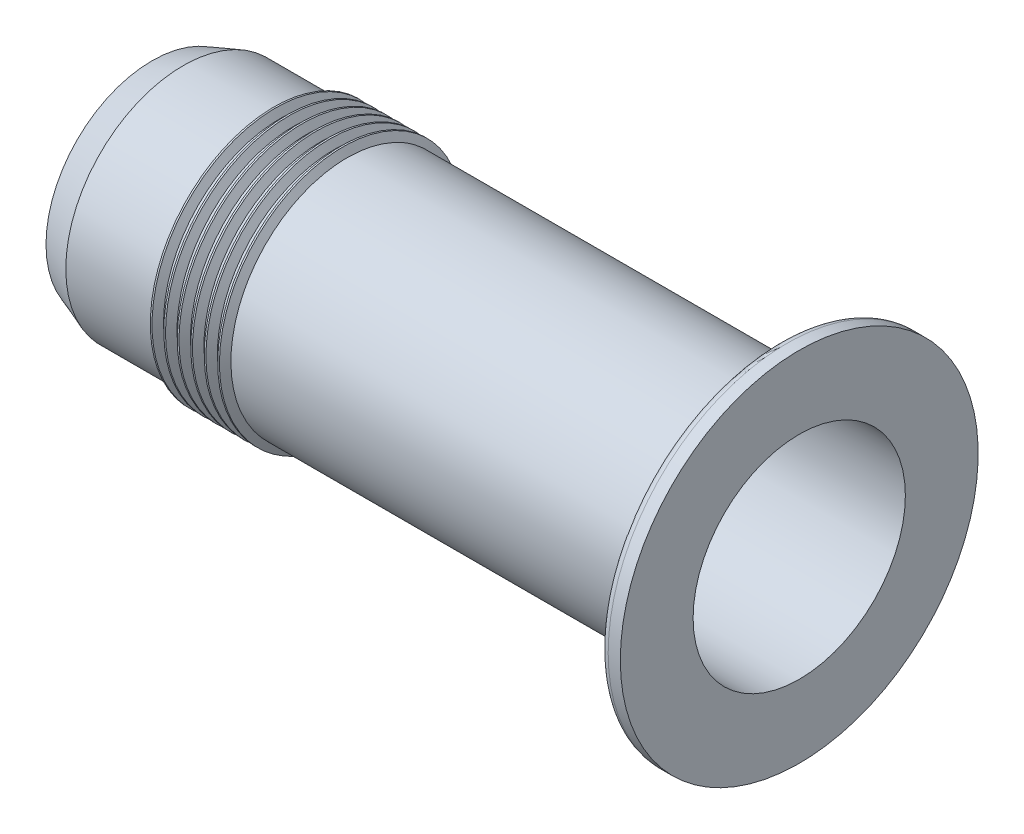
SolidWorks part; units mm, degrees
ref_plane "Front Plane" through (0, 0, 0) normal (0, 0, 1) x (1, 0, 0)
ref_plane "Top Plane" through (0, 0, 0) normal (0, 1, 0) x (1, 0, 0)
ref_plane "Right Plane" through (0, 0, 0) normal (1, 0, 0) x (0, 0, -1)
sketch "Sketch1" plane through (0, 0, 0) normal (0, 0, 1) x (1, 0, 0)
  line L0 (0, 0) -> (109.1124, 0) construction
  line L1 (0, 16.6624) -> (101.6, 16.6624)
  line L4 (19.05, 18.4404) -> (98.425, 18.4404)
  line L5 (101.6, 18.4404) -> (101.6, 16.6624)
  line L6 (0, 16.6624) -> (0, 0) construction
  line L7 (19.05, 18.4404) -> (4.885, 18.4404)
  line L9 (101.6, 18.4404) -> (101.6, 28.0924)
  line L10 (101.6, 28.0924) -> (98.425, 28.0924)
  line L11 (98.425, 28.0924) -> (98.425, 18.4404)
  line L12 (0, 16.6624) -> (4.885, 18.4404)
  dimension "D1" = 16.6624
  dimension "D2" = 1.778
  dimension "D3" = 11.43
  dimension "D4" = 3.175
  dimension "D5" = 101.6
  dimension "D6" = 20
revolve "Revolve1" add sketch "Sketch1" angle 360 about L0
thread "Thread2" pitch 2.1167 method extrude profile "Thread Profile4" start angle 0, offset 12.7, length 12.7, pitch 2.1167, diameter 36.8808
ref_plane "Plane4" through (17.585, 0, -18.4404) normal (0, -1, 0) x (0, 0, -1)
sketch "Thread Profile4" plane through (17.585, 0, -18.4404) normal (0, -1, 0) x (0, 0, -1)
  line L0 (0, 0) -> (0, 2.1167) construction
  line L1 (0, 0) -> (1.1457, 0.6615)
  line L2 (1.1457, 0.6615) -> (1.1457, 0.926)
  line L3 (1.1457, 0.926) -> (0, 1.5875)
  line L4 (1.1457, 0.7937) -> (0, 0.7937) construction
  line L11 (0, 0) -> (0, 1.5875)
  point P2 (0, 0)
  dimension "Pitch" = 2.1167
  dimension "Profile_Angle" = 60
  dimension "Profile_Land" = 0.2646
  dimension "Profile_Height" = 1.1457
fillet "Fillet1" radius 1.27 1 edges at (98.425, 0, 28.0924)
